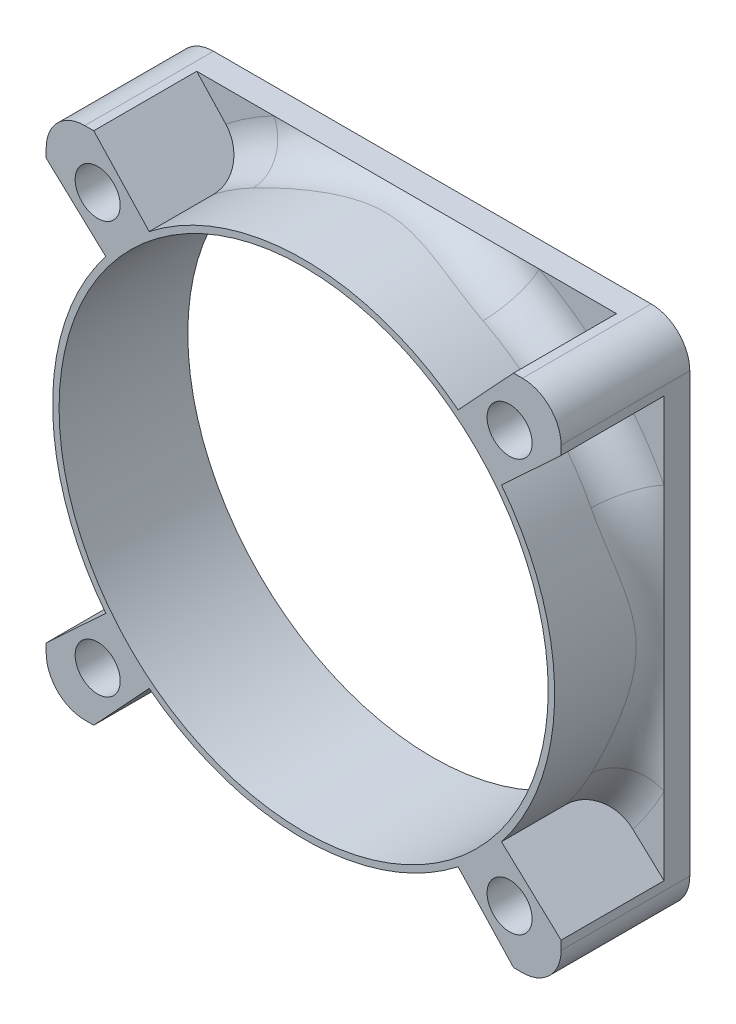
SolidWorks part; units mm, degrees
ref_plane "Plan de face" through (0, 0, 0) normal (0, 0, 1) x (1, 0, 0)
ref_plane "Plan de dessus" through (0, 0, 0) normal (0, 1, 0) x (1, 0, 0)
ref_plane "Plan de droite" through (0, 0, 0) normal (1, 0, 0) x (0, 0, -1)
sketch "Esquisse1" plane through (0, 0, 0) normal (0, 0, 1) x (1, 0, 0)
  line L1 (-20, 20) -> (20, 20)
  line L2 (-20, 20) -> (-20, -20)
  line L3 (-20, -20) -> (20, -20)
  line L4 (20, 20) -> (20, -20)
  dimension "D1" = 40
  dimension "D2" = 40
  dimension "D3" = 20
  dimension "D4" = 20
extrude "Boss.-Extru.1" add sketch "Esquisse1" along normal blind 10
fillet "Congé1" radius 3 4 edges at (20, -20, 5) (-20, -20, 5) (-20, 20, 5) (20, 20, 5)
sketch "Esquisse2" plane through (0, 0, 10) normal (0, 0, 1) x (1, 0, 0)
  line L1 (-20, 17) -> (-20, -17) construction
  line L5 (17, 20) -> (-17, 20) construction
  line L6 (20, -17) -> (20, 17) construction
  circle A0 centre (0, 0) radius 19
  circle A1 centre (-16, 16) radius 1.75
  circle A2 centre (16, 16) radius 1.75
  circle A3 centre (16, -16) radius 1.75
  circle A4 centre (-16, -16) radius 1.75
  dimension "D1" = 38
  dimension "D2" = 32
  dimension "D10" = 3.5
  dimension "D11" = 3.5
  dimension "D12" = 3.5
  dimension "D13" = 3.5
  dimension "D3" = 4
  dimension "D4" = 32
  dimension "D5" = 32
  dimension "D6" = 32
  dimension "D7" = 4
  dimension "D8" = 4
  dimension "D9" = 4
extrude "Enlèv. mat.-Extru.1" cut sketch "Esquisse2" against normal blind 10
sketch "Esquisse3" plane through (0, 0, 10) normal (0, 0, 1) x (1, 0, 0)
  line L0 (-15.3704, 12) -> (-20, 16.3064)
  line L1 (-20, 17) -> (-20, -17) construction
  line L2 (-12, 15.3704) -> (-16.3064, 20)
  line L3 (17, 20) -> (-17, 20) construction
  line L4 (12, 15.3704) -> (16.3064, 20)
  line L5 (15.3704, 12) -> (20, 16.3064)
  line L6 (20, -17) -> (20, 17) construction
  line L7 (15.3704, -12) -> (20, -16.3064)
  line L8 (12, -15.3704) -> (16.3064, -20)
  line L9 (-17, -20) -> (17, -20) construction
  line L10 (-12, -15.3704) -> (-16.3064, -20)
  line L11 (-15.3704, -12) -> (-20, -16.3064)
  line L12 (-16.3064, 20) -> (16.3064, 20)
  line L13 (20, 16.3064) -> (20, -16.3064)
  line L14 (16.3064, -20) -> (-16.3064, -20)
  line L16 (-20, 16.3064) -> (-20, -16.3064)
  arc A0 (-12, 15.3704) -> (12, 15.3704) centre (0, 0) cw
  arc A1 (15.3704, 12) -> (15.3704, -12) centre (0, 0) cw
  arc A2 (12, -15.3704) -> (-12, -15.3704) centre (0, 0) cw
  arc A3 (-15.3704, -12) -> (-15.3704, 12) centre (0, 0) cw
  circle A4 centre (-16, 16) radius 1.75 construction
  circle A5 centre (16, 16) radius 1.75 construction
  circle A6 centre (16, -16) radius 1.75 construction
  circle A7 centre (-16, -16) radius 1.75 construction
  dimension "D1" = 19.5
  dimension "D2" = 19.5
  dimension "D3" = 19.5
  dimension "D4" = 19.5
  dimension "D5" = 4
  dimension "D13" = 2.5
  dimension "D6" = 4
  dimension "D7" = 4
  dimension "D8" = 4
  dimension "D9" = 4
  dimension "D10" = 4
  dimension "D11" = 4
  dimension "D12" = 4
  dimension "D14" = 2.5
  dimension "D15" = 2.5
  dimension "D16" = 2.5
  dimension "D17" = 2.5
  dimension "D18" = 2.5
  dimension "D19" = 2.5
  dimension "D20" = 2.5
extrude "Enlèv. mat.-Extru.2" cut sketch "Esquisse3" against normal blind 8
fillet "Congé2" radius 3 4 edges at (-19.5, 0, 2) (0, -19.5, 2) (19.5, 0, 2) (0, 19.5, 2)
